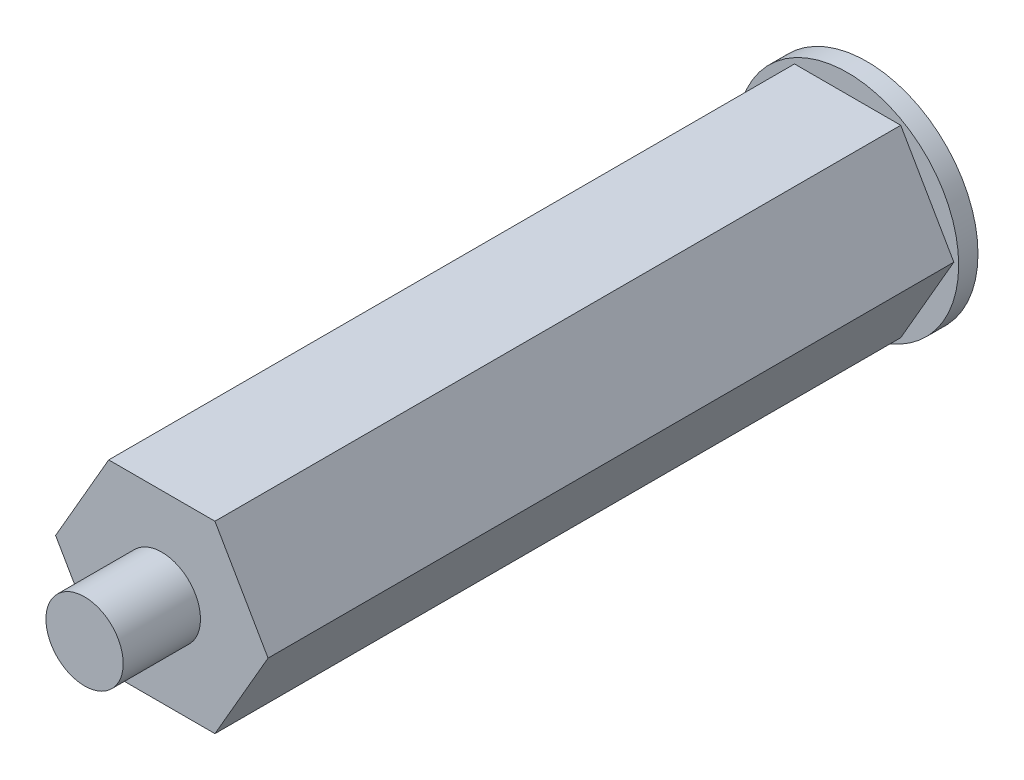
SolidWorks part; units mm, degrees
ref_plane "Front Plane" through (0, 0, 0) normal (0, 0, 1) x (1, 0, 0)
ref_plane "Top Plane" through (0, 0, 0) normal (0, 1, 0) x (1, 0, 0)
ref_plane "Right Plane" through (0, 0, 0) normal (1, 0, 0) x (0, 0, -1)
other "Configuration Table"
sketch "Sketch1" plane through (0, 0, 0) normal (0, 0, 1) x (1, 0, 0)
  line L1 (10.9985, 0) -> (5.4993, 9.525)
  line L2 (5.4993, 9.525) -> (-5.4993, 9.525)
  line L3 (-5.4993, 9.525) -> (-10.9985, 0)
  line L4 (-10.9985, 0) -> (-5.4993, -9.525)
  line L5 (-5.4993, -9.525) -> (5.4993, -9.525)
  line L6 (5.4993, -9.525) -> (10.9985, 0)
  circle A0 centre (0, 0) radius 9.525 construction
  circle A1 centre (0, 0) radius 9.525 construction
  dimension "D1" = 19.05
extrude "Boss-Extrude1" add sketch "Sketch1" along normal blind 35.5 and the other way blind 35.5
sketch "Sketch2" plane through (0, 0, -35.5) normal (0, 0, -1) x (-1, 0, 0)
  line L1 (7.1014, 0) -> (3.5507, 6.15)
  line L2 (3.5507, 6.15) -> (-3.5507, 6.15)
  line L3 (-3.5507, 6.15) -> (-7.1014, 0)
  line L4 (-7.1014, 0) -> (-3.5507, -6.15)
  line L5 (-3.5507, -6.15) -> (3.5507, -6.15)
  line L6 (3.5507, -6.15) -> (7.1014, 0)
  circle A0 centre (0, 0) radius 6.15 construction
  dimension "D1" = 12.3
extrude "Cut-Extrude1" cut sketch "Sketch2" against normal blind 6
sketch "Sketch4" plane through (0, 0, -35.5) normal (0, 0, -1) x (-1, 0, 0)
  circle A0 centre (0, 0) radius 8.5
  circle A1 centre (0, 0) radius 11.5
  dimension "D1" = 17
  dimension "D2" = 23
extrude "Boss-Extrude3" add sketch "Sketch4" along normal blind 2
sketch "Sketch5" plane through (0, 0, 35.5) normal (0, 0, 1) x (1, 0, 0)
  circle A0 centre (0, 0) radius 4
  dimension "D1" = 8
extrude "Boss-Extrude4" add sketch "Sketch5" along normal blind 8
